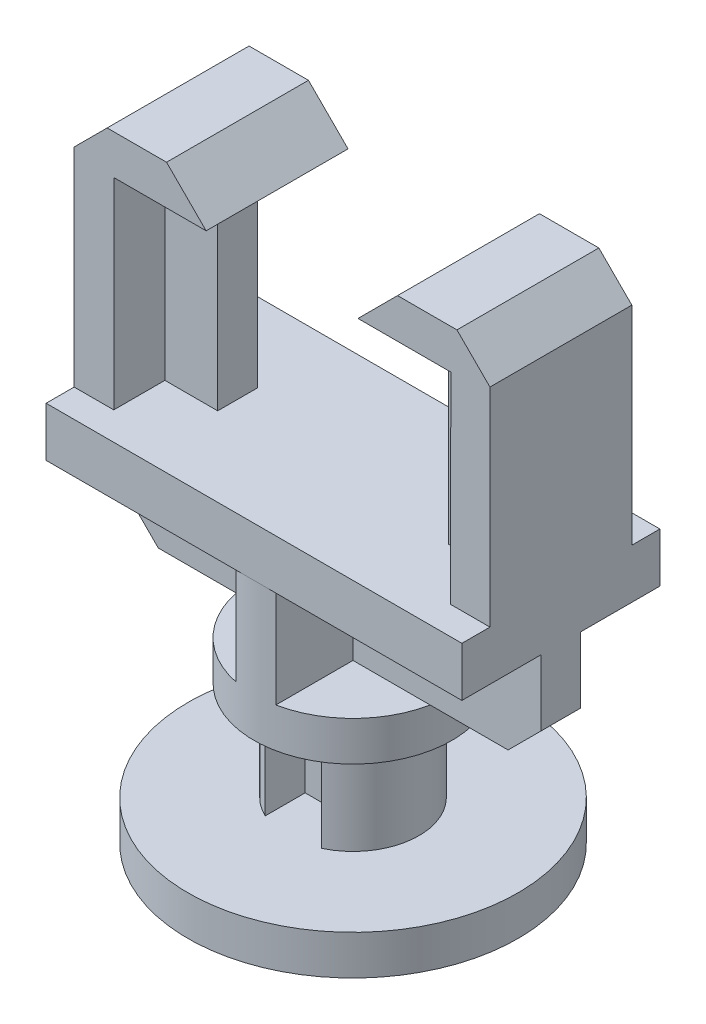
SolidWorks part; units mm, degrees
ref_plane "Front Plane" through (0, 0, 0) normal (0, 0, 1) x (1, 0, 0)
ref_plane "Top Plane" through (0, 0, 0) normal (0, 1, 0) x (1, 0, 0)
ref_plane "Right Plane" through (0, 0, 0) normal (1, 0, 0) x (0, 0, -1)
sketch "Sketch1" plane through (0, 0, 0) normal (0, 0, 1) x (1, 0, 0)
  line L0 (-3.5, 5.9) -> (-3.5, -5.9)
  line L1 (-6.3, -5.9) -> (6.3, -5.9)
  line L2 (-6.3, -5.9) -> (-6.3, 5.9)
  line L3 (-6.3, 5.9) -> (6.3, 5.9)
  line L4 (6.3, -5.9) -> (6.3, 5.9)
  line L5 (-6.3, -5.9) -> (6.3, 5.9) construction
  line L6 (-6.3, 5.9) -> (6.3, -5.9) construction
  line L7 (-2.3, 5.9) -> (-2.3, -5.9)
  line L8 (-6.3, 4.7) -> (6.3, 4.7)
  line L9 (-3.5, 5.9) -> (-2.3, 4.7)
  line L10 (0, 0) -> (0, -5.9) construction
  line L11 (2.3, 5.9) -> (2.3, -5.9)
  line L12 (3.5, 5.9) -> (2.3, 4.7)
  line L13 (3.5, 5.9) -> (3.5, -5.9)
  line L14 (-6.3, -5.9) -> (-6.3, 5.9)
  line L15 (6.3, -5.9) -> (6.3, 5.9)
  line L16 (-6.3, -1.4) -> (6.3, -1.4)
  point P0 (0, 0)
  dimension "D1" = 12.6
  dimension "D2" = 11.8
  dimension "D3" = 2.8
  dimension "D4" = 4
  dimension "D5" = 1.2
  dimension "D6" = 4.5
extrude "Boss-Extrude1" add sketch "Sketch1" along normal mid plane 1.2 contours L2 L8 L0 L3 | L9 L0 L8 | L14 L16 L0 L8 | L16 L2 L1 L0 | L16 L0 L1 L7 | L16 L7 L1 L11 | L16 L11 L1 L13 | L16 L13 L1 L4 | L13 L16 L15 L8 | L13 L12 L8 | L3 L13 L8 L4 region at (-3.1, 5.1, 0) region at (-4.9, 5.3, 0) region at (-4.9, 1.65, 0) region at (-2.9, -3.65, 0) region at (-4.9, -3.65, 0) region at (0, -3.65, 0) region at (3.1, 5.1, 0) region at (4.9, 5.3, 0) region at (2.9, -3.65, 0) region at (4.9, 1.65, 0) region at (4.9, -3.65, 0)
sketch "Sketch2" plane through (0, 0, 0.6) normal (0, 0, 1) x (1, 0, 0)
  line L0 (3.5, 4.7) -> (6.3, 4.7)
  line L1 (6.3, -5.9) -> (6.3, 5.9) construction
  line L2 (3.5, 5.9) -> (6.3, 5.9) construction
  line L3 (5.1, 5.9) -> (5.1, -5.9)
  line L4 (-6.3, -5.9) -> (6.3, -5.9) construction
  line L5 (-6.3, -2.9) -> (6.3, -2.9)
  line L6 (-6.3, -5.9) -> (-6.3, 5.9) construction
  line L7 (3.5, -1.4) -> (6.3, -1.4)
  line L8 (0, 0) -> (0, -2.4354) construction
  line L9 (-3.5, -1.4) -> (3.5, -1.4) construction
  line L10 (-3.5, -1.4) -> (-6.3, -1.4)
  line L11 (-5.1, 5.9) -> (-5.1, -5.9)
  line L12 (-3.5, 4.7) -> (-6.3, 4.7)
  dimension "D1" = 1.2
  dimension "D2" = 8.8
sketch "Sketch3" plane through (0, 0, 0.6) normal (0, 0, 1) x (1, 0, 0)
  line L0 (-6.3, 4.7) -> (-6.3, 5.9)
  line L1 (-6.3, 5.9) -> (-5.1, 5.9)
  line L2 (-5.1, 5.9) -> (-3.5, 5.9)
  line L3 (-3.5, 5.9) -> (-2.3, 4.7)
  line L4 (-2.3, 4.7) -> (-3.5, 4.7)
  line L5 (-3.5, 4.7) -> (-5.1, 4.7)
  line L6 (-5.1, 5.9) -> (-5.1, -5.9) construction
  line L7 (-5.1, 4.7) -> (-5.1, -1.4)
  line L8 (-3.5, -1.4) -> (-6.3, -1.4) construction
  line L9 (-6.3, 4.7) -> (-6.3, -2.9)
  line L10 (-6.3, -2.9) -> (6.3, -2.9)
  line L11 (6.3, -2.9) -> (6.3, 5.9)
  line L12 (6.3, 5.9) -> (3.5, 5.9)
  line L13 (3.5, 5.9) -> (6.3, 5.9) construction
  line L14 (3.5, 5.9) -> (2.3, 4.7)
  line L15 (2.3, 4.7) -> (3.5, 4.7)
  line L17 (3.5, -1.4) -> (-5.1, -1.4)
  line L18 (3.5, 4.7) -> (5.1159, 4.7)
  line L19 (3.5, 4.7) -> (6.3, 4.7) construction
  line L20 (5.1159, 4.7) -> (5.1, -1.4)
  line L21 (5.1, 5.9) -> (5.1, -5.9) construction
  line L22 (3.5, -1.4) -> (6.3, -1.4) construction
  line L23 (5.1, -1.4) -> (3.5, -1.4)
extrude "Boss-Extrude2" add sketch "Sketch3" along normal blind 1.55
mirror "Mirror1" about plane through (0, 0, 0) normal (0, 0, 1) of "Boss-Extrude2", "Boss-Extrude1"
sketch "Sketch5" plane through (0, 0, -2.15) normal (0, 0, -1) x (-1, 0, 0)
  line L0 (-5.1, -1.4) -> (-6.3, -1.4)
  line L1 (-6.3, -2.9) -> (-6.3, 5.9) construction
  line L2 (-6.3, -1.4) -> (-6.3, -2.9)
  line L3 (-6.3, -2.9) -> (6.3, -2.9)
  line L4 (6.3, -2.9) -> (6.3, -1.4)
  line L5 (6.3, 5.9) -> (6.3, -2.9) construction
  line L6 (6.3, -1.4) -> (-5.1, -1.4)
extrude "Boss-Extrude3" add sketch "Sketch5" along normal blind 0.85
mirror "Mirror2" about plane through (0, 0, 0) normal (0, 0, 1) of "Boss-Extrude3"
sketch "Sketch6" plane through (0, -5.9, 0) normal (0, -1, 0) x (1, 0, 0)
  circle A0 centre (0, 0) radius 3
  dimension "D1" = 6
extrude "Boss-Extrude4" add sketch "Sketch6" along normal blind 1.2
sketch "Sketch7" plane through (0, -5.9, 0) normal (0, 1, 0) x (1, 0, 0)
  line L1 (-0.6, -4.5) -> (0.6, -4.5)
  line L2 (-0.6, -4.5) -> (-0.6, 4.5)
  line L3 (-0.6, 4.5) -> (0.6, 4.5)
  line L4 (0.6, -4.5) -> (0.6, 4.5)
  line L5 (-0.6, -4.5) -> (0.6, 4.5) construction
  line L6 (-0.6, 4.5) -> (0.6, -4.5) construction
  circle A0 centre (0, 0) radius 3
  point P0 (0, 0)
  arc M5 (2.9394, 0.6) -> (-2.9394, 0.6) centre (0, 0) ccw
  line M6 (-2.9394, 0.6) -> (2.9394, 0.6)
  dimension "D3" = 6
  dimension "D1" = 1.2
  dimension "D2" = 9
extrude "Boss-Extrude5" add sketch "Sketch7" along direction (0, 1, 0) on the side of the normal up to surface (3 mm away) contours L2 A0 L4 M6 | L4 L2 M6 M5 region at (0, -5.9, 1.19) region at (0, -5.9, -1.79) up to face at (0, -2.9, 1.8)
sketch "Sketch8" plane through (0, -7.1, 0) normal (0, -1, 0) x (1, 0, 0)
  circle A0 centre (0, 0) radius 2
  dimension "D1" = 4
extrude "Boss-Extrude6" add sketch "Sketch8" along normal blind 3
sketch "Sketch9" plane through (0, -10.1, 0) normal (0, -1, 0) x (1, 0, 0)
  line L1 (-0.85, -4) -> (0.85, -4)
  line L2 (-0.85, -4) -> (-0.85, 4)
  line L3 (-0.85, 4) -> (0.85, 4)
  line L4 (0.85, -4) -> (0.85, 4)
  line L5 (-0.85, -4) -> (0.85, 4) construction
  line L6 (-0.85, 4) -> (0.85, -4) construction
  line L7 (-0.85, -0.6) -> (0.85, -0.6)
  line L8 (-0.85, -0.6) -> (-0.85, 0.6)
  line L9 (-0.85, 0.6) -> (0.85, 0.6)
  line L10 (0.85, -0.6) -> (0.85, 0.6)
  line L11 (-0.85, -0.6) -> (0.85, 0.6) construction
  line L12 (-0.85, 0.6) -> (0.85, -0.6) construction
  circle A0 centre (0, 0) radius 2
  point P0 (0, 0)
  dimension "D3" = 4
  dimension "D1" = 1.7
  dimension "D2" = 8
  dimension "D4" = 1.2
extrude "Cut-Extrude1" cut sketch "Sketch9" against normal up to surface (3 mm away) contours L7 L2 L4 | L2 L9 L4 L7 region at (0, -10.1, -1.2702) region at (0, -10.1, 1.2702) up to face at (0, -7.1, -2)
sketch "Sketch10" plane through (0, -10.1, 0) normal (0, -1, 0) x (1, 0, 0)
  circle A0 centre (0, 0) radius 5
  dimension "D1" = 10
extrude "Boss-Extrude7" add sketch "Sketch10" along normal blind 1.2
chamfer "Chamfer1" distance 1 angle 45 4 edges at (-6.3, 5.9, 0) (-6.3, -5.9, 0) (6.3, -5.9, 0) (6.3, 5.9, 0)
